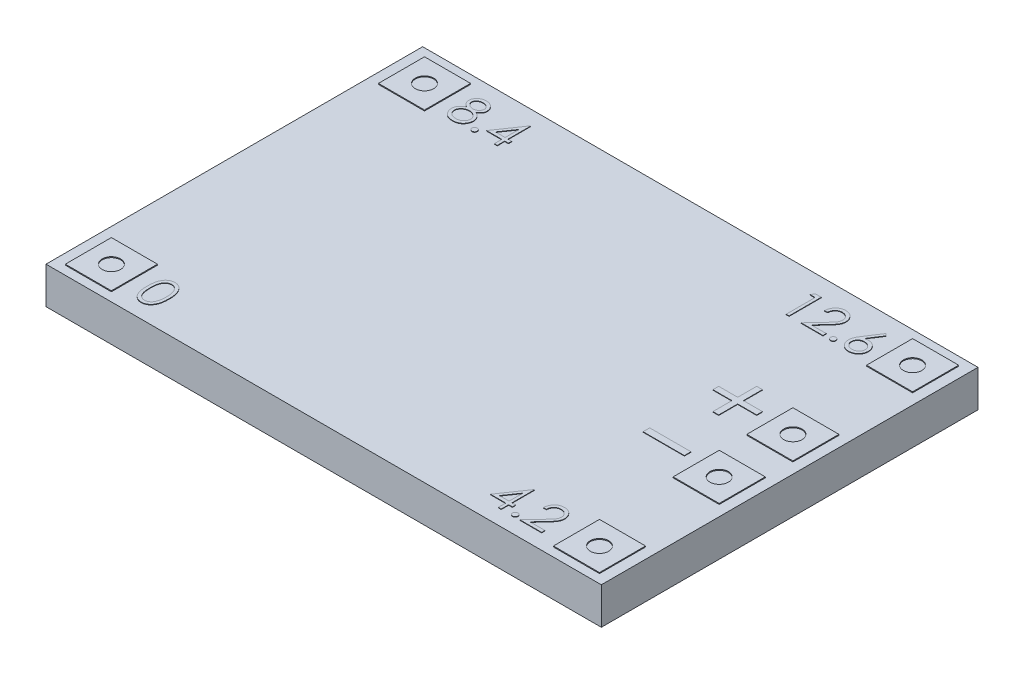
SolidWorks part; units mm, degrees
ref_plane "Спереди" through (0, 0, 0) normal (0, 0, 1) x (1, 0, 0)
ref_plane "Сверху" through (0, 0, 0) normal (0, 1, 0) x (1, 0, 0)
ref_plane "Справа" through (0, 0, 0) normal (1, 0, 0) x (0, 0, -1)
sketch "Эскиз1" plane through (0, 0, 0) normal (0, 1, 0) x (1, 0, 0)
  line L1 (30.15, -20.45) -> (-30.15, -20.45)
  line L2 (30.15, -20.45) -> (30.15, 20.45)
  line L3 (30.15, 20.45) -> (-30.15, 20.45)
  line L4 (-30.15, -20.45) -> (-30.15, 20.45)
  line L5 (30.15, -20.45) -> (-30.15, 20.45) construction
  line L6 (30.15, 20.45) -> (-30.15, -20.45) construction
  point P0 (0, 0)
  dimension "D1" = 40.9
  dimension "D2" = 60.3
extrude "Бобышка-Вытянуть1" add sketch "Эскиз1" along normal blind 4
sketch "Эскиз2" plane through (0, 4, 0) normal (0, 1, 0) x (1, 0, 0)
  line L0 (0, 6.7905) -> (0, -5.6858) construction
  line L5 (-24, 14.5) -> (-29, 19.5) construction
  line L6 (-24, 19.5) -> (-29, 14.5) construction
  line L7 (-24, -19.5) -> (-29, -19.5)
  line L8 (-24, -19.5) -> (-24, -14.5)
  line L9 (-24, -14.5) -> (-29, -14.5)
  line L10 (-29, -19.5) -> (-29, -14.5)
  line L11 (-24, -19.5) -> (-29, -14.5) construction
  line L12 (-24, -14.5) -> (-29, -19.5) construction
  line L17 (-29, 19.5) -> (-29, 14.5)
  line L18 (-24, 14.5) -> (-29, 14.5)
  line L23 (-24, 19.5) -> (-24, 14.5)
  line L24 (-24, 19.5) -> (-29, 19.5)
  line L25 (-22.3533, 0) -> (10.7868, 0) construction
  line L26 (24, -14.5) -> (29, -19.5) construction
  line L27 (24, -19.5) -> (29, -14.5) construction
  line L28 (24, 19.5) -> (29, 14.5) construction
  line L29 (24, 14.5) -> (29, 19.5) construction
  line L30 (24, 19.5) -> (29, 19.5)
  line L31 (24, 19.5) -> (24, 14.5)
  line L32 (24, 14.5) -> (29, 14.5)
  line L33 (29, 19.5) -> (29, 14.5)
  line L34 (29, -19.5) -> (29, -14.5)
  line L35 (24, -14.5) -> (29, -14.5)
  line L36 (24, -19.5) -> (24, -14.5)
  line L37 (24, -19.5) -> (29, -19.5)
  line L38 (29, -6.5) -> (24, -1.5) construction
  line L39 (29, 1.5) -> (24, 1.5)
  line L40 (29, 1.5) -> (29, 6.5)
  line L41 (29, 6.5) -> (24, 6.5)
  line L42 (24, 1.5) -> (24, 6.5)
  line L43 (29, 1.5) -> (24, 6.5) construction
  line L44 (29, 6.5) -> (24, 1.5) construction
  line L45 (29, -1.5) -> (24, -6.5) construction
  line L46 (24, -1.5) -> (24, -6.5)
  line L47 (29, -6.5) -> (24, -6.5)
  line L48 (29, -1.5) -> (29, -6.5)
  line L49 (29, -1.5) -> (24, -1.5)
  circle A3 centre (-26.5, -17) radius 1
  circle A4 centre (-26.5, 17) radius 1
  circle A5 centre (26.5, 17) radius 1
  circle A6 centre (26.5, -17) radius 1
  circle A7 centre (26.5, 4) radius 1
  circle A8 centre (26.5, -4) radius 1
  point P5 (-26.5, -17)
  point P11 (-26.5, 17)
  point P24 (26.5, 17)
  point P25 (26.5, -17)
  point P33 (26.5, 4)
  point P42 (26.5, -4)
  dimension "D1" = 2
  dimension "D2" = 34
  dimension "D3" = 53
  dimension "D6" = 5
  dimension "D4" = 5
  dimension "D5" = 5
  dimension "D7" = 8
extrude "Бобышка-Вытянуть2" add sketch "Эскиз2" along normal blind 0.1 separate body
sketch "Эскиз3" plane through (0, 4, 0) normal (0, 1, 0) x (1, 0, 0)
  text T0 "+" font "Century Gothic" height 7
  text T1 "-" font "Century Gothic" height 7
  text T2 "12.6"
  text T3 "8.4"
  text T4 "0"
  text T5 "4.2\r\n"
extrude "Бобышка-Вытянуть3" add sketch "Эскиз3" along normal blind 0.05 separate body
